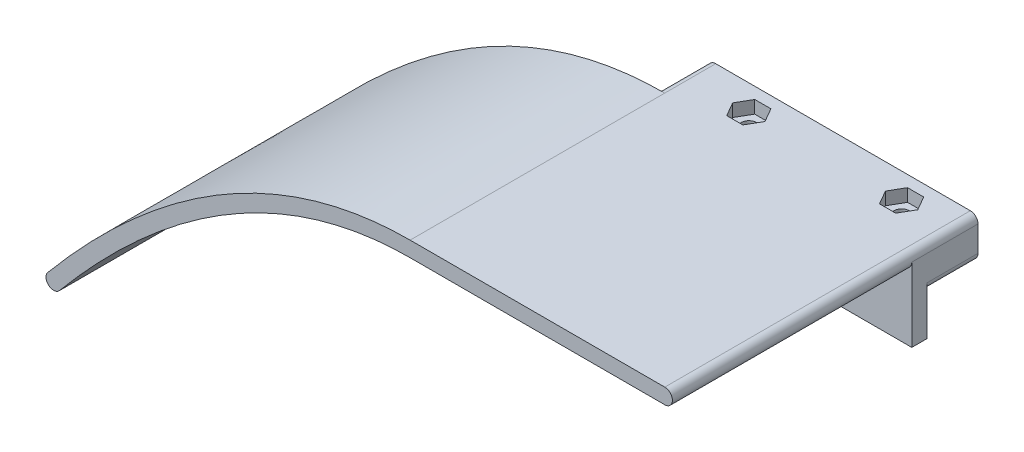
SolidWorks part; units mm, degrees
material "ABS"
ref_plane "前视基准面" through (0, 0, 0) normal (0, 0, 1) x (1, 0, 0)
ref_plane "上视基准面" through (0, 0, 0) normal (0, 1, 0) x (1, 0, 0)
ref_plane "右视基准面" through (0, 0, 0) normal (1, 0, 0) x (0, 0, -1)
sketch "草图1" plane through (0, 0, 0) normal (0, 0, 1) x (1, 0, 0)
  line L0 (-25, -1.5) -> (-60.3652, -1.5) construction
  line L1 (-25, -1.5) -> (25, -1.5)
  line L2 (-25, -1.5) -> (-25, 1.5) construction
  line L4 (25, -1.5) -> (25, 1.5) construction
  line L5 (-25, -1.5) -> (25, 1.5) construction
  line L6 (-25, 1.5) -> (25, -1.5) construction
  line L7 (-60.3652, -1.5) -> (-93.8498, -41.5) construction
  line L8 (-25, 1.5) -> (25, 1.5)
  arc A0 (25, 1.5) -> (25, -1.5) centre (25, 0) cw
  arc A2 (-96.1502, -39.5743) -> (-93.8498, -41.5) centre (-95, -40.5372) ccw
  spline S0 degree 2 poles (-25, -1.5) (-60.3652, -1.5) (-93.8498, -41.5) knots 0 0 0 1 1 1
  spline S1 degree 1 poles (-25, 1.5) (-96.1502, -39.5743) knots 0 0 1 1 construction
  spline S2 degree 2 poles (-25, 1.5) (-38.9325, 1.4849) (-61.4589, -8.275) (-83.417, -24.345) (-96.1502, -39.5743) knots 0 0 0 0.375 0.625 1 1 1
  point P0 (0, 0)
  dimension "D3" = 70
  dimension "D4" = 40
  dimension "D1" = 50
  dimension "D2" = 3
  dimension "D5" = 52.1653
extrude "凸台-拉伸1" add sketch "草图1" along normal blind 50 contours L8 A0 L1 S0 A2 S2
sketch "草图2" plane through (0, 0, 0) normal (0, 0, -1) x (-1, 0, 0)
  line L0 (25, 1.5) -> (-25, 1.5) construction
  line L1 (25, 1.5) -> (-25, 1.5)
  line L2 (-26.5, 0) -> (-26.5, -42.0372)
  line L3 (95, -42.0372) -> (-26.5, -42.0372)
  arc A0 (93.8498, -41.5) -> (96.1502, -39.5743) centre (95, -40.5372) ccw construction
  arc A1 (-25, 1.5) -> (-25, -1.5) centre (-25, 0) ccw construction
  arc A2 (95, -42.0372) -> (96.1502, -39.5743) centre (95, -40.5372) ccw
  arc A3 (-25, 1.5) -> (-26.5, 0) centre (-25, 0) ccw
  spline S0 degree 2 poles (-610.3232, -1884.1816) (-203.9546, 106.7189) (61.4589, -8.275) (297.6137, -181.1045) (393.4396, -2011.6322) knots -6.738961 -6.738961 -6.738961 0.375 0.625 7.09675 7.09675 7.09675 only from (25, 1.5) to (96.1502, -39.5743) construction
  spline S1 degree 2 poles (25, 1.5) (38.9325, 1.4849) (61.4589, -8.275) (83.417, -24.345) (96.1502, -39.5743) knots 0 0 0 0.375 0.625 1 1 1
extrude "凸台-拉伸2" add sketch "草图2" against normal blind 3
sketch "草图3" plane through (0, 0, 0) normal (0, 0, -1) x (-1, 0, 0)
  line L0 (-25, 1.5) -> (25, 1.5)
  line L1 (-26.5, 0) -> (-26.5, -5)
  line L2 (-26.5, 0) -> (-26.5, -42.0372) construction
  line L3 (26.5, 0) -> (26.5, -5)
  line L4 (-25, -6.5) -> (25, -6.5)
  arc A0 (-25, 1.5) -> (-26.5, 0) centre (-25, 0) ccw construction
  arc A1 (-26.5, -5) -> (-25, -6.5) centre (-25, -5) ccw
  arc A2 (25, -6.5) -> (26.5, -5) centre (25, -5) ccw
  arc A3 (26.5, 0) -> (25, 1.5) centre (25, 0) ccw
  arc A4 (-25, 1.5) -> (-26.5, 0) centre (-25, 0) ccw
  dimension "D1" = 8
extrude "凸台-拉伸3" add sketch "草图3" along normal blind 10
sketch "草图4" plane through (0, 1.5, 0) normal (0, 1, 0) x (1, 0, 0)
  line L0 (-25, 5) -> (-15.7274, 5) construction
  line L3 (-25, 10) -> (25, 10) construction
  line L4 (26.5, -3) -> (26.5, 10) construction
  circle A0 centre (-13.5, 5) radius 1.5
  circle A1 centre (16.5, 5) radius 1.5
  dimension "D1" = 5
  dimension "D2" = 3
  dimension "D3" = 30
  dimension "D4" = 10
extrude "切除-拉伸1" cut sketch "草图4" against normal through all contours A0 | A1
sketch "草图5" plane through (0, 0, 0) normal (0, 0, -1) x (-1, 0, 0)
  line L0 (-26.5, -14.5) -> (33.5, -14.5)
  line L1 (-26.5, -5) -> (-26.5, -42.0372) construction
  line L2 (-26.5, -42.0372) -> (95, -42.0372) construction
  line L3 (-25, -6.5) -> (25, -6.5) construction
  line L4 (-26.5, -14.5) -> (-26.5, -42.0372)
  line L5 (-26.5, -42.0372) -> (61.0372, -42.0372)
  arc A0 (33.5, -14.5) -> (61.0372, -42.0372) centre (33.5, -42.0372) cw
  dimension "D1" = 8
  dimension "D2" = 60
extrude "切除-拉伸2" cut sketch "草图5" against normal through all
sketch "草图6" plane through (0, 1.5, 0) normal (0, 1, 0) x (1, 0, 0)
  line L1 (-11.9123, 7.75) -> (-15.0877, 7.75)
  line L2 (-15.0877, 7.75) -> (-16.6754, 5)
  line L3 (-16.6754, 5) -> (-15.0877, 2.25)
  line L4 (-15.0877, 2.25) -> (-11.9123, 2.25)
  line L5 (-11.9123, 2.25) -> (-10.3246, 5)
  line L6 (-10.3246, 5) -> (-11.9123, 7.75)
  line L7 (18.0877, 7.75) -> (14.9123, 7.75)
  line L8 (14.9123, 7.75) -> (13.3246, 5)
  line L9 (13.3246, 5) -> (14.9123, 2.25)
  line L10 (14.9123, 2.25) -> (18.0877, 2.25)
  line L11 (18.0877, 2.25) -> (19.6754, 5)
  line L12 (19.6754, 5) -> (18.0877, 7.75)
  circle A0 centre (-13.5, 5) radius 2.75 construction
  circle A1 centre (16.5, 5) radius 2.75 construction
  dimension "D1" = 5.5
extrude "切除-拉伸3" cut sketch "草图6" along normal through all from offset 2.5 offset against normal yes
fillet "圆角1" radius 2 1 edges at (-61.0372, -42.0372, 1.5)
